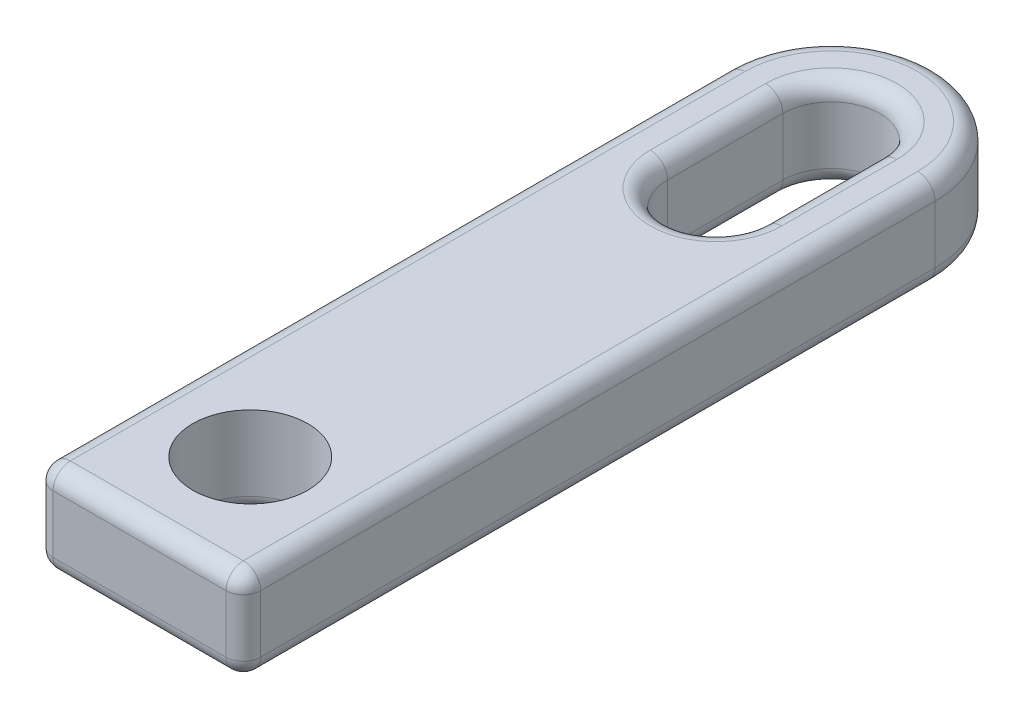
SolidWorks part; units mm, degrees
ref_plane "Front Plane" through (0, 0, 0) normal (0, 0, 1) x (1, 0, 0)
ref_plane "Top Plane" through (0, 0, 0) normal (0, 1, 0) x (1, 0, 0)
ref_plane "Right Plane" through (0, 0, 0) normal (1, 0, 0) x (0, 0, -1)
sketch "Sketch1" plane through (0, 0, 0) normal (0, 1, 0) x (1, 0, 0)
  line L0 (0, -7.4492) -> (0, -12.4492) construction
  line L3 (-4.5, -17.4492) -> (-4.5, -7.4492)
  line L4 (4.5, -27.4492) -> (4.5, -7.4492)
  line L5 (-4.5, -17.4492) -> (-4.5, -37.4492)
  line L6 (-4.5, -37.4492) -> (4.5, -37.4492)
  line L7 (4.5, -37.4492) -> (4.5, -27.4492)
  line L8 (2.1, -7.4492) -> (2.1, -12.4492)
  line L9 (-2.1, -7.4492) -> (-2.1, -12.4492)
  line L10 (-4.5, -7.4492) -> (4.5, -7.4492) construction
  arc A4 (2.1, -7.4492) -> (-2.1, -7.4492) centre (0, -7.4492) ccw
  circle A5 centre (0, -32.6492) radius 2.5
  arc A6 (-2.1, -12.4492) -> (2.1, -12.4492) centre (0, -12.4492) ccw
  arc A7 (-4.5, -7.4492) -> (4.5, -7.4492) centre (0, -7.4492) cw
  point P3 (0, -9.9492)
  point P17 (0, -7.4492)
  dimension "D5" = 4.8
  dimension "D2" = 2.1
  dimension "D1" = 5
  dimension "D4" = 20
  dimension "D3" = 10
  dimension "D6" = 25
  dimension "D9" = 9
extrude "Boss-Extrude1" add sketch "Sketch1" along normal blind 4
fillet "Fillet1" radius 0.75 19 edges at (-4.5, 4, 22.4492) (-4.5, 2, 37.4492) (0, 4, 37.4492) (2.1, 0, 9.9492) (0, 0, 14.5492) (-2.1, 0, 9.9492) (0, 0, 5.3492) (-4.5, 0, 22.4492) (0, 0, 37.4492) (0, 4, 2.9492) (0, 0, 2.9492) (4.5, 2, 37.4492) (4.5, 4, 22.4492) (4.5, 0, 22.4492) (0, 4, 5.3492) (2.1, 4, 9.9492) (0, 4, 14.5492) (-2.1, 4, 9.9492) (0, 0, 35.1492)
